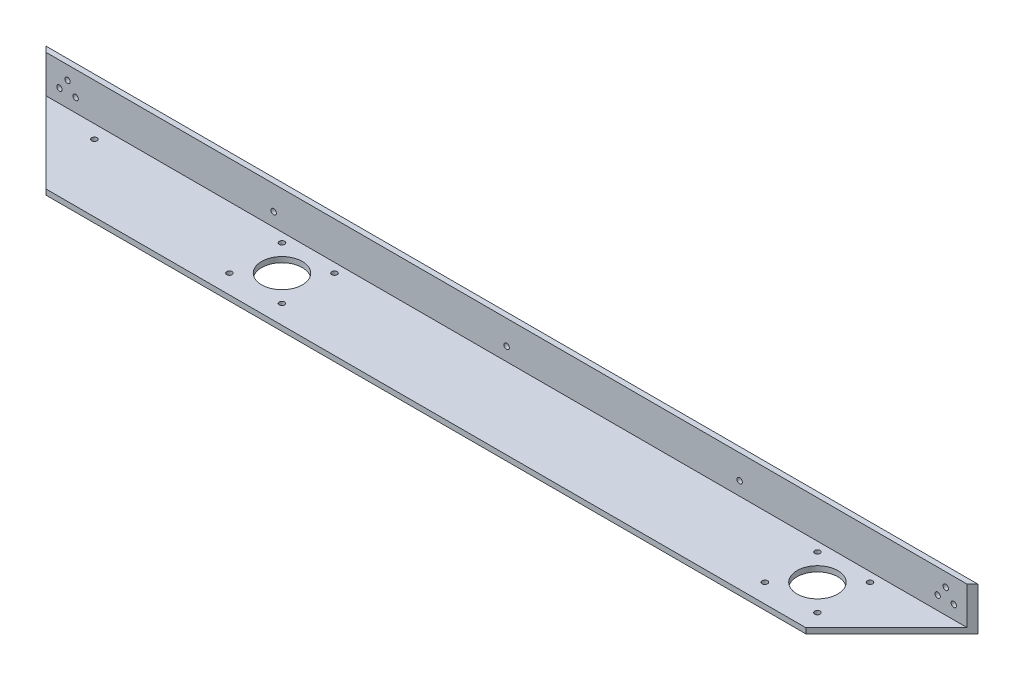
SolidWorks part; units mm, degrees
ref_plane "Front Plane" through (0, 0, 0) normal (0, 0, 1) x (1, 0, 0)
ref_plane "Top Plane" through (0, 0, 0) normal (0, 1, 0) x (1, 0, 0)
ref_plane "Right Plane" through (0, 0, 0) normal (1, 0, 0) x (0, 0, -1)
sketch "Sketch1" plane through (0, 0, 0) normal (1, 0, 0) x (0, 0, -1)
  line L0 (0, 0) -> (-50.8, 0)
  line L1 (-50.8, 0) -> (-50.8, 3.175)
  line L2 (-50.8, 3.175) -> (-3.175, 3.175)
  line L3 (-3.175, 3.175) -> (-3.175, 25.4)
  line L4 (-3.175, 25.4) -> (0, 25.4)
  line L5 (0, 25.4) -> (0, 0)
  dimension "LHeight" = 25.4
  dimension "LWidth" = 50.8
  dimension "LMaterialThickness" = 3.175
  dimension "D1" = 47.625
  dimension "D2" = 22.225
  dimension "D3" = 3.175
extrude "Boss-Extrude1" add sketch "Sketch1" along normal blind 550
chamfer "Chamfer7" distance 50.8 angle 45 1 edges at (0, 1.5875, 50.8)
chamfer "Chamfer8" distance 50.8 angle 45 1 edges at (550, 1.5875, 50.8)
sketch "BotthomHoles-Sketch2" plane through (0, 3.175, 0) normal (0, 1, 0) x (1, 0, 0)
  line L0 (546.825, -3.175) -> (3.175, -3.175) construction
  line L1 (550, 0) -> (0, 0) construction
  circle A0 centre (479.425, -24.175) radius 12
  circle A2 centre (463.925, -8.675) radius 1.5875
  circle A3 centre (494.925, -8.675) radius 1.5875
  circle A6 centre (463.925, -39.675) radius 1.5875
  circle A7 centre (494.925, -39.675) radius 1.5875
  circle A8 centre (39.6875, -11.1125) radius 1.5875
  circle A10 centre (178.925, -39.675) radius 1.5875
  circle A11 centre (147.925, -39.675) radius 1.5875
  circle A12 centre (178.925, -8.675) radius 1.5875
  circle A13 centre (147.925, -8.675) radius 1.5875
  circle A14 centre (163.425, -24.175) radius 12
  dimension "D9" = 3.175
  dimension "D10" = 24
  dimension "D13" = 3.175
  dimension "D2" = 8.675
  dimension "D5" = 15.5
  dimension "D6" = 31
  dimension "D7" = 15.5
  dimension "D8" = 31
  dimension "D11" = 21
  dimension "D3" = 70.575
  dimension "D4" = 11.1125
  dimension "D12" = 39.6875
  dimension "D15" = 31
  dimension "D16" = 15.5
  dimension "D17" = 316
extrude "BottomHoles-Cut-Extrude1" cut sketch "BotthomHoles-Sketch2" against normal through all
sketch "RightSideHoles-Sketch3" plane through (0, 0, 0) normal (0, 0, -1) x (-1, 0, 0)
  line L0 (-550, 0) -> (-550, 25.4) construction
  line L1 (0, 0) -> (0, 25.4) construction
  line L2 (-550, 25.4) -> (0, 25.4) construction
  circle A1 centre (-534.125, 17.4625) radius 1.5875
  circle A2 centre (-538.8875, 11.1125) radius 1.5875
  circle A3 centre (-529.3625, 11.1125) radius 1.5875
  circle A4 centre (-11.1125, 11.1125) radius 1.5875
  circle A5 centre (-20.6375, 11.1125) radius 1.5875
  circle A6 centre (-15.875, 17.4625) radius 1.5875
  circle A8 centre (-412.5, 11.1125) radius 1.5875
  circle A9 centre (-275, 11.1125) radius 1.5875
  circle A10 centre (-137.5, 11.1125) radius 1.5875
  dimension "D4" = 11.1125
  dimension "D7" = 3.175
  dimension "D2" = 15.875
  dimension "D6" = 15.875
  dimension "D8" = 137.5
  dimension "D9" = 137.5
  dimension "D10" = 137.5
  dimension "D5" = 11.1125
  dimension "D11" = 11.1125
  dimension "D3" = 7.9375
  dimension "D12" = 20.6375
  dimension "D13" = 20.6375
extrude "RightSideHoles-Cut-Extrude2" cut sketch "RightSideHoles-Sketch3" against normal through all
equation "\"LowerRailWidth\"= 2.00in"
equation "\"LowerRailHeight\"= 1.00in"
equation "\"RailThickness\"= .125in'Spec"
equation "\"SideRailHoleY1FromEdge\"= \"HoleOffsetFromEdge\""
equation "\"SideRailHoleX1FromSide\"= \"HoleOffsetFromSide\""
equation "\"StepperHoleDiameter\"= 24mm"
equation "\"StepperMountingHoleDiameter\"= 3.175mm"
equation "\"SideRailLength\"= 550mm"
equation "\"StepperMountingHoleDistance\"= 31mm'Spec"
equation "\"VSWidth\"= 1.25in'Spec"
equation "\"StepperMountingHoleOffsetFromLeftOrRightSide\"= \"StepperMountingHoleOffsetFromItsSide\" + \"RailThickness\""
equation "\"HoleOffsetFromEdge\"= \"RailThickness\" * 2.5"
equation "\"HoleOffsetFromSide\"= \"RailThickness\" * 3.5"
equation "\"StepperMountingHoleOffsetFromItsSide\"= 5.5mm'Spec"
equation "\"SideRailHoleX2FromSide\"= \"VSWidth\" - \"HoleOffsetFromEdge\" - \"RailThickness\"'Equals 20.6375"
equation "\"FasteningHoleDiameter\"= .125in"
equation "\"SideRailHoleY2FromSide\"= \"HoleOffsetFromSide\""
equation "\"LHeight@Sketch1\"=\"LowerRailHeight\""
equation "\"LWidth@Sketch1\"=\"LowerRailWidth\""
equation "\"D1@Chamfer7\"=\"LowerRailWidth\""
equation "\"D1@Chamfer8\"=\"LowerRailWidth\""
equation "\"D2@BotthomHoles-Sketch2\" = \"StepperMountingHoleOffsetFromLeftOrRightSide\""
equation "\"D5@BotthomHoles-Sketch2\" = \"StepperMountingHoleDistance\" / 2"
equation "\"D6@BotthomHoles-Sketch2\" = \"StepperMountingHoleDistance\""
equation "\"D7@BotthomHoles-Sketch2\" = \"StepperMountingHoleDistance\" / 2"
equation "\"D8@BotthomHoles-Sketch2\" = \"StepperMountingHoleDistance\""
equation "\"D9@BotthomHoles-Sketch2\" = \"StepperMountingHoleDiameter\""
equation "\"D10@BotthomHoles-Sketch2\" = \"StepperHoleDiameter\""
equation "\"D2@RightSideHoles-Sketch3\"=\"VSMidSideRailHoleXFromSideToCenter\" - \"RailThickness\""
equation "\"D4@RightSideHoles-Sketch3\" = \"SideRailHoleY2FromSide\""
equation "\"D7@RightSideHoles-Sketch3\" = \"FasteningHoleDiameter\""
equation "\"D1@Boss-Extrude1\"=\"SideRailLength\""
equation "\"D6@RightSideHoles-Sketch3\"=\"VSMidSideRailHoleXFromSideToCenter\" - \"RailThickness\""
equation "\"BedThirdSize\"= 70mm"
equation "\"BedInnerSquareWidth\"= \"BedThirdSize\" * 3'Equals 210"
equation "\"BedInnerSquareLength\"= \"BedInnerSquareWidth\""
equation "\"BedLWidth\"= \"BedThirdSize\"'Equals 70"
equation "\"BedLength\"= \"BedInnerSquareLength\" + \"BedLWidth\" * 2 + \"BedIncreasedByLength\"'Equals 350"
equation "\"DistanceBetweenFrontToBackStepperHoles\"= \"BedLength\" - \"DistanceFromBedFrontToFirstLeftStepperHole\"'Equals 316"
equation "\"D3@BotthomHoles-Sketch2\"=\"DistanceFromFrontSideToFirstLeftStepperHole\""
equation "\"DistanceFromBedFrontToFirstLeftStepperHole\"= \"LeadScrewNutPadSize\" + 10mm'Equals 34"
equation "\"DistanceFromFrontSideToBedFront\"= \"RailThickness\" + \"BeltTensionerDepth\" + 10mm'Equals 36.575"
equation "\"20TGT2PulleyDiameter\"= 17.9mm'Spec"
equation "\"BeltTensionerBackWallThickness\"= 4mm"
equation "\"BeltTensionerSpaceBetweenPulleyAndWall\"= 1.5mm"
equation "\"BeltTensionerInnerDepth\"= \"20TGT2PulleyDiameter\" + \"BeltTensionerSpaceBetweenPulleyAndWall\""
equation "\"BeltTensionerDepth\"= \"BeltTensionerBackWallThickness\" + \"BeltTensionerInnerDepth\"'Equals 23.4"
equation "\"BedIncreasedByLength\"= 0mm"
equation "\"LowerCornerBlockWidth\"= \"LowerRailWidth\" - \"RailThickness\" * 2'Room for left front stepper"
equation "\"D4@BotthomHoles-Sketch2\"=\"LowerCornerBlockY1FromSide\""
equation "\"D12@BotthomHoles-Sketch2\"=\"CornerEnclosureOffset\""
equation "\"D13@BotthomHoles-Sketch2\"=\"FasteningHoleDiameter\""
equation "\"CornerEnclosureOffset\"= \"LowerCornerBlockWidth\" - \"HoleOffsetFromEdge\" + \"RailThickness\""
equation "\"LowerCornerBlockY1FromSide\"= \"HoleOffsetFromSide\""
equation "\"D15@BotthomHoles-Sketch2\"=\"StepperMountingHoleDistance\""
equation "\"D16@BotthomHoles-Sketch2\"=\"StepperMountingHoleDistance\"/2"
equation "\"D17@BotthomHoles-Sketch2\"=\"DistanceBetweenFrontToBackStepperHoles\""
equation "\"DistanceFromFrontSideToFirstLeftStepperHole\"= \"DistanceFromFrontSideToBedFront\" + \"DistanceFromBedFrontToFirstLeftStepperHole\"'Equals 70.575"
equation "\"LeadScrewNutMountingHoleFlangeDiameter\"= 22mm'Spec"
equation "\"LeadScrewNutPadSize\"= \"LeadScrewNutMountingHoleFlangeDiameter\" + 2mm'Equals 24"
equation "\"LeftOrRightEnclosureOffsets\"= \"SideRailLength\" / 4"
equation "\"D8@RightSideHoles-Sketch3\"=\"LeftOrRightEnclosureOffsets\""
equation "\"D9@RightSideHoles-Sketch3\"=\"LeftOrRightEnclosureOffsets\""
equation "\"D10@RightSideHoles-Sketch3\"=\"LeftOrRightEnclosureOffsets\""
equation "\"D5@RightSideHoles-Sketch3\"=\"SideRailHoleX1FromSide\""
equation "\"D11@RightSideHoles-Sketch3\"=\"SideRailHoleX1FromSide\""
equation "\"D3@RightSideHoles-Sketch3\"=\"SideRailHoleY1FromEdge\""
equation "\"VSMidSideRailHoleXFromSideToCenter\"= \"RailThickness\" * 6"
equation "\"D12@RightSideHoles-Sketch3\"=\"SideRailHoleX2FromSide\""
equation "\"D13@RightSideHoles-Sketch3\"=\"SideRailHoleX2FromSide\""
